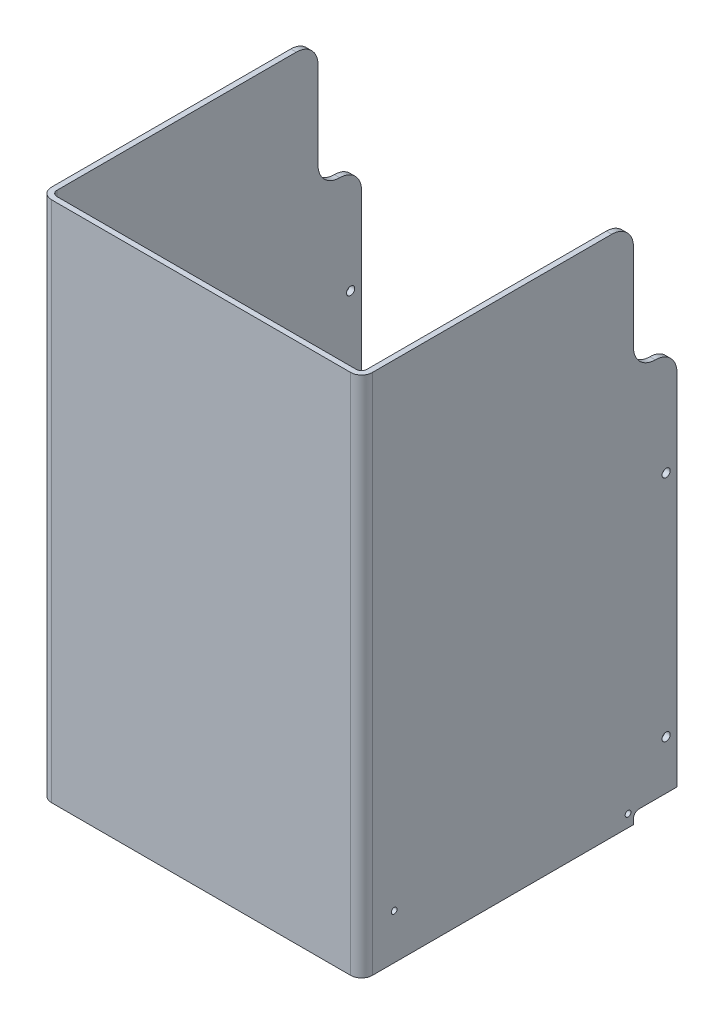
SolidWorks part; units mm, degrees
material "PC High Viscosity"
ref_plane "Front Plane" through (0, 0, 0) normal (0, 0, 1) x (1, 0, 0)
ref_plane "Top Plane" through (0, 0, 0) normal (0, 1, 0) x (1, 0, 0)
ref_plane "Right Plane" through (0, 0, 0) normal (1, 0, 0) x (0, 0, -1)
sketch "Sketch1" plane through (0, 0, 0) normal (0, 1, 0) x (1, 0, 0)
  line L0 (0, 0) -> (0, -368.3)
  line L1 (0, -368.3) -> (374.65, -368.3)
  line L2 (374.65, -368.3) -> (374.65, 0)
  line L3 (374.65, 0) -> (368.3, 0)
  line L4 (368.3, 0) -> (368.3, -361.95)
  line L5 (368.3, -361.95) -> (6.35, -361.95)
  line L6 (6.35, -361.95) -> (6.35, 0)
  line L7 (6.35, 0) -> (0, 0)
  dimension "D1" = 361.95
  dimension "D2" = 361.95
  dimension "D3" = 6.35
  dimension "D4" = 6.35
extrude "Boss-Extrude1" add sketch "Sketch1" along normal blind 609.6
fillet "Fillet1" radius 6.35 2 edges at (368.3, 304.8, 361.95) (6.35, 304.8, 361.95)
fillet "Fillet2" radius 12.7 2 edges at (374.65, 304.8, 368.3) (0, 304.8, 368.3)
sketch "Sketch2" plane through (374.65, 0, 0) normal (1, 0, 0) x (0, 0, -1)
  line L0 (0, 0) -> (-50.8, 0)
  line L1 (0, 0) -> (0, 12.7)
  line L2 (-50.8, 0) -> (-50.8, 12.7)
  line L3 (0, 12.7) -> (-50.8, 12.7)
  line L4 (-355.6, 0) -> (0, 0) construction
  dimension "D1" = 12.7
  dimension "D2" = 50.8
extrude "Cut-Extrude1" cut sketch "Sketch2" against normal through all
sketch "Sketch4" plane through (374.65, 0, 0) normal (1, 0, 0) x (0, 0, -1)
  line L1 (0, 609.6) -> (-50.8, 609.6)
  line L2 (0, 609.6) -> (0, 457.2)
  line L3 (0, 457.2) -> (-50.8, 457.2)
  line L4 (-50.8, 609.6) -> (-50.8, 457.2)
  dimension "D1" = 50.8
  dimension "D2" = 152.4
extrude "Cut-Extrude2" cut sketch "Sketch4" against normal through all
sketch "Sketch5" plane through (374.65, 0, 0) normal (1, 0, 0) x (0, 0, -1)
  line L0 (-0.4419, 12.7) -> (0, 15.8441) construction
  line L1 (-0.4419, 12.7) -> (-355.7253, 62.6318) construction
  line L2 (0, 15.8441) -> (-355.2834, 65.7759) construction
  line L3 (-355.7253, 62.6318) -> (-355.2834, 65.7759) construction
  line L4 (0, 12.7) -> (-50.8, 12.7) construction
  line L5 (-355.6, 0) -> (-50.8, 0) construction
  line L6 (-330.2, 52.6321) -> (-57.15, 14.2574) construction
  line L7 (0, 457.2) -> (0, 12.7) construction
  circle A0 centre (-330.2, 52.6321) radius 3.3782
  circle A1 centre (-57.15, 14.2574) radius 3.3782
  point P14 (0, 0)
  point P15 (0, 0)
  dimension "D4" = 6.35
  dimension "D5" = 6.7564
  dimension "D1" = 3.175
  dimension "D2" = 8
  dimension "D3" = 358.775
  dimension "D6" = 57.15
  dimension "D7" = 330.2
extrude "Cut-Extrude3" cut sketch "Sketch5" against normal through all
sketch "Sketch6" plane through (374.65, 0, 0) normal (1, 0, 0) x (0, 0, -1)
  line L0 (0, 12.7) -> (-50.8, 12.7) construction
  line L2 (0, 457.2) -> (0, 12.7) construction
  circle A0 centre (-12.7, 69.85) radius 4.7625
  circle A1 centre (-12.7, 336.55) radius 4.7625
  point P6 (0, 0)
  dimension "D1" = 57.15
  dimension "D3" = 9.525
  dimension "D2" = 266.7
  dimension "D4" = 12.7
extrude "Cut-Extrude4" cut sketch "Sketch6" against normal through all
fillet "Fillet3" radius 25.4 6 edges at (3.175, 457.2, 0) (371.475, 457.2, 0) (371.475, 457.2, 50.8) (3.175, 457.2, 50.8) (3.175, 609.6, 50.8) (371.475, 609.6, 50.8)
fillet "Fillet4" radius 6.35 2 edges at (3.175, 12.7, 50.8) (371.475, 12.7, 50.8)
